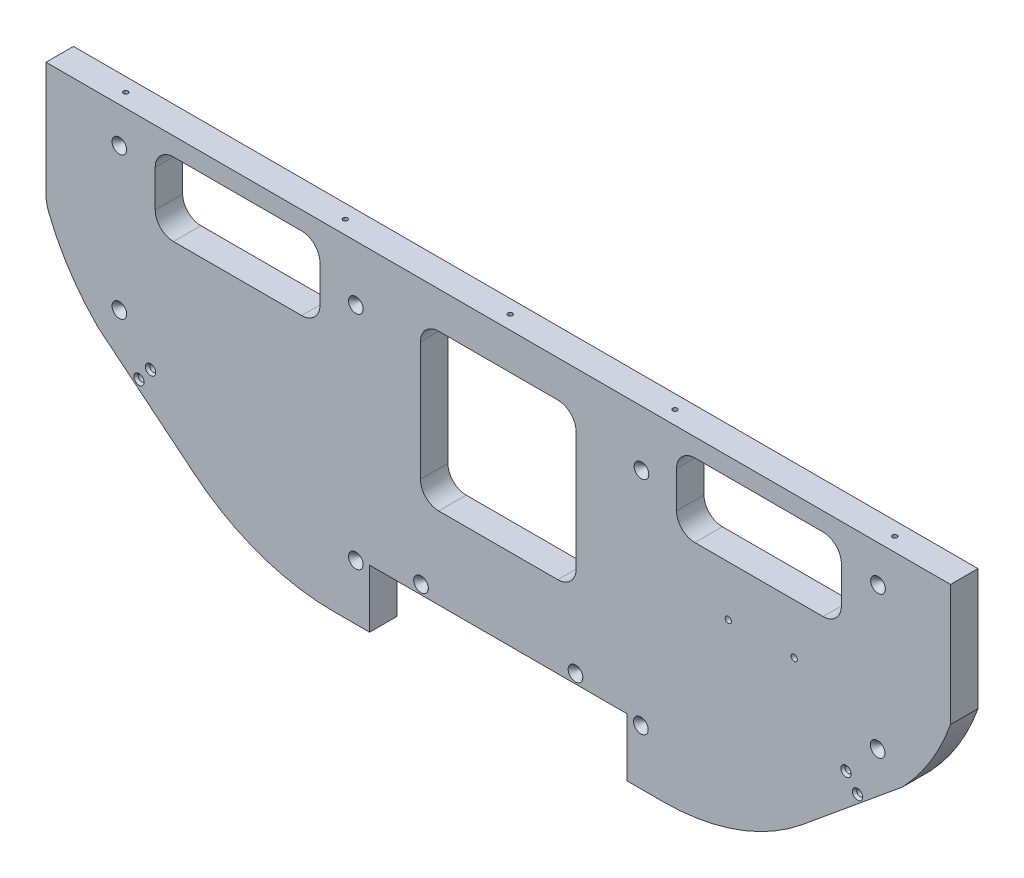
SolidWorks part; units mm, degrees
material "MDF"
ref_plane "Front Plane" through (0, 0, 0) normal (0, 0, 1) x (1, 0, 0)
ref_plane "Top Plane" through (0, 0, 0) normal (0, 1, 0) x (1, 0, 0)
ref_plane "Right Plane" through (0, 0, 0) normal (1, 0, 0) x (0, 0, -1)
sketch "Sketch1" plane through (0, 0, 0) normal (0, 0, 1) x (1, 0, 0)
  line L0 (-394.3667, -87.3125) -> (-394.3667, 23.8125) construction
  line L2 (-618.7884, -233.3625) -> (-593.7567, -233.3625) construction
  line L3 (-394.3667, -87.3125) -> (-394.3667, -3.175)
  line L4 (-497.3744, -199.0142) -> (-427.755, -141.5981)
  line L5 (-709.3267, -233.3625) -> (-593.7567, -233.3625)
  line L6 (-709.3267, -3.175) -> (-709.3267, -233.3625) construction
  line L7 (-1021.7467, -3.175) -> (-396.9067, -3.175) construction
  line L8 (-394.3667, -3.175) -> (-709.3267, -3.175)
  line L9 (-1021.7467, -3.175) -> (-396.9067, -3.175) construction
  line L10 (-976.0267, -152.2395) -> (-918.7391, -199.0142) construction
  line L11 (-1021.7467, -87.3125) -> (-1021.7467, -20.955) construction
  line L12 (-985.5517, -144.4625) -> (-918.7391, -199.0142)
  line L13 (-1021.7467, -87.3125) -> (-1021.7467, -3.175)
  line L14 (-822.3567, -233.3625) -> (-709.3267, -233.3625)
  line L15 (-709.3267, -3.175) -> (-1021.7467, -3.175)
  arc A0 (-427.755, -141.5981) -> (-394.3667, -87.3125) centre (-538.0037, -36.3792) ccw construction
  arc A1 (-593.7567, -233.3625) -> (-497.3744, -199.0142) centre (-593.7567, -80.9625) ccw construction
  arc A2 (-427.755, -141.5981) -> (-394.3667, -87.3125) centre (-538.0037, -36.3792) ccw
  arc A3 (-593.7567, -233.3625) -> (-497.3744, -199.0142) centre (-593.7567, -80.9625) ccw
  arc A4 (-918.7391, -199.0142) -> (-822.3567, -233.3625) centre (-822.3567, -80.9625) ccw construction
  arc A5 (-1021.7467, -87.3125) -> (-985.5517, -144.4625) centre (-878.1098, -36.3792) ccw construction
  arc A6 (-918.7391, -199.0142) -> (-822.3567, -233.3625) centre (-822.3567, -80.9625) ccw
  arc A7 (-1021.7467, -87.3125) -> (-985.5517, -144.4625) centre (-878.1098, -36.3792) ccw
  point P13 (-709.3267, -3.175)
extrude "Boss-Extrude1" add sketch "Sketch1" along normal blind 19.05
hole_wizard "5/64 (0.07813) Diameter Hole1" positions "Sketch2" profile "Sketch3" hole size "5/64" standard "ANSI Inch"
sketch "Sketch2" plane through (-708.0567, 15.875, 6128.5599) normal (0, 1, 0) x (1, 0, 0)
  line L1 (-1.27, 6109.5099) -> (-1.27, 6338.7449) construction
  point P0 (-262.8265, 6157.4524)
  point P6 (-98.7933, 6157.4524)
  point P18 (-262.8265, 6233.6524)
  point P19 (-98.7933, 6233.6524)
  point P22 (-262.8265, 6309.8524)
  point P23 (-98.7933, 6309.8524)
  point P24 (-267.97, 6119.0349)
  point P34 (-115.57, 6119.0349)
  point P37 (-1.27, 6119.0349)
  point P40 (113.03, 6119.0349)
  point P44 (265.43, 6119.0349)
  point P55 (96.2533, 6309.8524)
  point P56 (260.2865, 6309.8524)
  point P59 (96.2533, 6233.6524)
  point P60 (260.2865, 6233.6524)
  point P63 (96.2533, 6157.4524)
  point P64 (260.2865, 6157.4524)
sketch "Sketch3" plane through (-970.8832, 15.875, -28.8925) normal (1, 0, 0) x (0, 0, 1)
  line L0 (0, 0) -> (0, 39.0539)
  line L1 (0, 39.0539) -> (1.5875, 38.1)
  line L2 (1.5875, 38.1) -> (1.5875, 4.0177)
  line L3 (1.5875, 4.0177) -> (5.08, 0)
  line L4 (5.08, 0) -> (0, 0)
  line L5 (-1.5875, 4.0177) -> (-5.08, 0) construction
  line L6 (0, 39.0539) -> (-1.5875, 38.1) construction
  line L7 (0, -6.35) -> (0, 107.95) construction
  dimension "Hole Dia." = 3.175
  dimension "Hole Depth" = 38.1
  dimension "Near C'Sink Dia." = 10.16
  dimension "Near C'Sink Angle" = 82
  dimension "Drill Angle" = 118
hole_wizard "5/64 (0.07813) Diameter Hole2" positions "Sketch4" profile "Sketch5" hole size "5/64" standard "ANSI Inch"
sketch "Sketch4" plane through (-708.0567, 1936.854, 19.05) normal (0, 0, 1) x (-1, 0, 0)
  line L23 (262.8265, 2088.1084) -> (262.8265, 2038.7486)
  line L24 (262.8265, 2038.7486) -> (262.8265, 1989.3888)
  line L25 (262.8265, 1989.3888) -> (262.8265, 2038.7486)
  line L26 (262.8265, 2038.7486) -> (262.8265, 1989.3888)
  line L27 (262.8265, 1989.3888) -> (262.8265, 1940.029)
  line L33 (98.7933, 2170.2165) -> (98.7933, 2131.8519)
  line L35 (98.7933, 2131.8519) -> (98.7933, 2093.4873)
  line L36 (98.7933, 2093.4873) -> (98.7933, 2055.1227)
  line L37 (98.7933, 2055.1227) -> (98.7933, 2016.7581)
  line L38 (98.7933, 2016.7581) -> (98.7933, 1978.3935)
  line L39 (98.7933, 1978.3935) -> (98.7933, 1940.029)
  line L44 (89.2683, 2123.544) -> (53.561, 2123.544)
  line L46 (53.561, 2123.544) -> (17.8537, 2123.544)
  line L47 (17.8537, 2123.544) -> (-17.8537, 2123.544)
  line L48 (-17.8537, 2123.544) -> (-53.561, 2123.544)
  line L49 (-53.561, 2123.544) -> (-89.2683, 2123.544)
  line L53 (0, 2170.2165) -> (-0.3175, 1940.029) construction
  line L55 (-99.3221, 1978.6668) -> (-99.4279, 1940.3024)
  line L56 (-99.2163, 2017.0312) -> (-99.3221, 1978.6668)
  line L57 (-99.1104, 2055.3957) -> (-99.2163, 2017.0312)
  line L58 (-99.0046, 2093.7601) -> (-99.1104, 2055.3957)
  line L59 (-98.8988, 2132.1245) -> (-99.0046, 2093.7601)
  line L60 (-98.7929, 2170.489) -> (-98.8988, 2132.1245)
  line L61 (-263.3243, 1990.1145) -> (-263.4605, 1940.7549)
  line L62 (-263.1882, 2039.4741) -> (-263.3243, 1990.1145)
  line L63 (-263.3243, 1990.1145) -> (-263.1882, 2039.4741)
  line L64 (-263.1882, 2039.4741) -> (-263.3243, 1990.1145)
  line L65 (-263.052, 2088.8338) -> (-263.1882, 2039.4741)
  point P71 (262.8265, 1964.7089)
  point P79 (262.8265, 2063.4285)
  point P95 (98.7933, 2131.8519)
  point P103 (98.7933, 1978.3935)
  point P126 (53.561, 2123.544)
  point P134 (-53.561, 2123.544)
  point P162 (-99.3221, 1978.6668)
  point P166 (-98.8988, 2132.1245)
  point P167 (-263.1201, 2064.1539)
  point P169 (-263.3924, 1965.4347)
sketch "Sketch5" plane through (-444.6643, -28.5807, 19.05) normal (1, 0, 0) x (0, -1, 0)
  line L0 (0, 0) -> (0, 38.6962)
  line L1 (0, 38.6962) -> (0.9923, 38.1)
  line L2 (0.9923, 38.1) -> (0.9923, 4.7024)
  line L3 (0.9923, 4.7024) -> (5.08, 0)
  line L4 (5.08, 0) -> (0, 0)
  line L5 (-0.9923, 4.7024) -> (-5.08, 0) construction
  line L6 (0, 38.6962) -> (-0.9923, 38.1) construction
  line L7 (0, -6.35) -> (0, 107.95) construction
  dimension "Hole Dia." = 1.9845
  dimension "Hole Depth" = 38.1
  dimension "Near C'Sink Dia." = 10.16
  dimension "Near C'Sink Angle" = 82
  dimension "Drill Angle" = 118
sketch "Sketch6" plane through (0, 0, 0) normal (0, 0, -1) x (-1, 0, 0)
  line L1 (797.325, -233.3625) -> (618.7884, -233.3625)
  line L2 (797.325, -233.3625) -> (797.325, -193.04)
  line L3 (797.325, -193.04) -> (618.7884, -193.04)
  line L4 (618.7884, -233.3625) -> (618.7884, -193.04)
extrude "Cut-Extrude1" cut sketch "Sketch6" against normal up to next
fillet "Fillet1" radius 25.4 2 edges at (-985.5517, -144.4625, 9.525) (-1021.7467, -87.3125, 9.525)
hole_wizard "#6 Clearance Hole1" positions "Sketch7" profile "Sketch8" hole size "#6" standard "ANSI Inch" end condition up to next
sketch "Sketch7" plane through (0, 0, 19.05) normal (0, 0, 1) x (1, 0, 0)
  arc A0 (-504.7297, -98.0667) -> (-504.7297, -104.8742) centre (-502.7993, -101.4705) ccw construction
  arc A1 (-550.4497, -98.0667) -> (-550.4497, -104.8742) centre (-548.5193, -101.4705) ccw construction
  point P0 (-502.7993, -101.4705)
  point P2 (-548.5193, -101.4705)
sketch "Sketch8" plane through (-502.7993, -101.4705, 19.05) normal (1, 0, 0) x (0, -1, 0)
  line L0 (0, 0) -> (0, 19.05)
  line L1 (0, 19.05) -> (2.1526, 19.05)
  line L2 (2.1526, 19.05) -> (2.1526, 0)
  line L5 (2.1526, 0) -> (0, 0)
  line L11 (0, -6.35) -> (0, 107.95) construction
  dimension "Thru Hole Dia." = 4.3053
  dimension "Thru Hole Depth" = 19.05
hole_wizard "CSK for #6 Flat Head Machine Screw (100)1" positions "Sketch9" profile "Sketch10" countersink size "#6" standard "ANSI Inch" end condition up to next
sketch "Sketch9" plane through (0, 0, 19.05) normal (0, 0, 1) x (1, 0, 0)
  point P0 (-957.2382, -161.4319)
  point P3 (-949.206, -151.5944)
  point P6 (-466.9052, -151.5924)
  point P9 (-458.8731, -161.4298)
sketch "Sketch10" plane through (-957.2382, -161.4319, 19.05) normal (1, 0, 0) x (0, -1, 0)
  line L0 (0, 0) -> (0, 19.05)
  line L1 (0, 19.05) -> (2.1526, 19.05)
  line L2 (2.1526, 19.05) -> (2.1526, 1.5998)
  line L3 (2.1526, 1.5998) -> (3.5433, 0)
  line L5 (3.5433, 0) -> (0, 0)
  line L6 (-2.1526, 1.5998) -> (-3.5433, 0) construction
  line L11 (0, -6.35) -> (0, 107.95) construction
  dimension "Thru Hole Dia." = 4.3053
  dimension "Thru Hole Depth" = 19.05
  dimension "Near C'Sink Dia." = 7.0866
  dimension "Near C'Sink Angle" = 82
sketch "Sketch12" plane through (0, 0, 19.05) normal (0, 0, 1) x (1, 0, 0)
  line L0 (-708.0567, -193.04) -> (-708.0567, -3.175) construction
  line L1 (-797.325, -193.04) -> (-618.7884, -193.04) construction
  line L2 (-394.3667, -3.175) -> (-1021.7467, -3.175) construction
  line L3 (-970.8832, -27.8549) -> (-806.85, -27.8549) construction
  line L4 (-806.85, -41.5396) -> (-806.85, -27.8549) construction
  line L5 (-584.3968, -15.875) -> (-470.0968, -15.875)
  line L6 (-831.7166, -66.675) -> (-946.0166, -66.675)
  line L7 (-831.7166, -66.675) -> (-831.7166, -15.875)
  line L8 (-831.7166, -15.875) -> (-946.0166, -15.875)
  line L9 (-946.0166, -66.675) -> (-946.0166, -15.875)
  line L10 (-831.7166, -66.675) -> (-946.0166, -15.875) construction
  line L11 (-831.7166, -15.875) -> (-946.0166, -66.675) construction
  line L12 (-470.0968, -66.675) -> (-470.0968, -15.875)
  line L13 (-584.3968, -66.675) -> (-470.0968, -66.675)
  line L14 (-584.3968, -66.675) -> (-584.3968, -15.875)
  line L15 (-394.3667, -3.175) -> (-1021.7467, -3.175) construction
  line L16 (-654.0817, -136.525) -> (-762.0317, -136.525)
  line L17 (-654.0817, -136.525) -> (-654.0817, -28.575)
  line L18 (-654.0817, -28.575) -> (-762.0317, -28.575)
  line L19 (-762.0317, -136.525) -> (-762.0317, -28.575)
  line L20 (-654.0817, -136.525) -> (-762.0317, -28.575) construction
  line L21 (-654.0817, -28.575) -> (-762.0317, -136.525) construction
  point P9 (-888.8666, -27.8549)
  point P10 (-888.8666, -41.275)
  point P20 (-708.0567, -82.55)
  dimension "D1" = 114.3
  dimension "D2" = 50.8
  dimension "D3" = 12.7
  dimension "D4" = 107.95
  dimension "D5" = 107.95
  dimension "D6" = 25.4
extrude "Cut-Extrude2" cut sketch "Sketch12" against normal through all
fillet "Fillet2" radius 12.7 12 edges at (-584.3968, -66.675, 9.525) (-584.3968, -15.875, 9.525) (-470.0968, -15.875, 9.525) (-470.0968, -66.675, 9.525) (-654.0817, -136.525, 9.525) (-654.0817, -28.575, 9.525) (-762.0317, -28.575, 9.525) (-762.0317, -136.525, 9.525) (-946.0166, -66.675, 9.525) (-946.0166, -15.875, 9.525) (-831.7166, -15.875, 9.525) (-831.7166, -66.675, 9.525)
